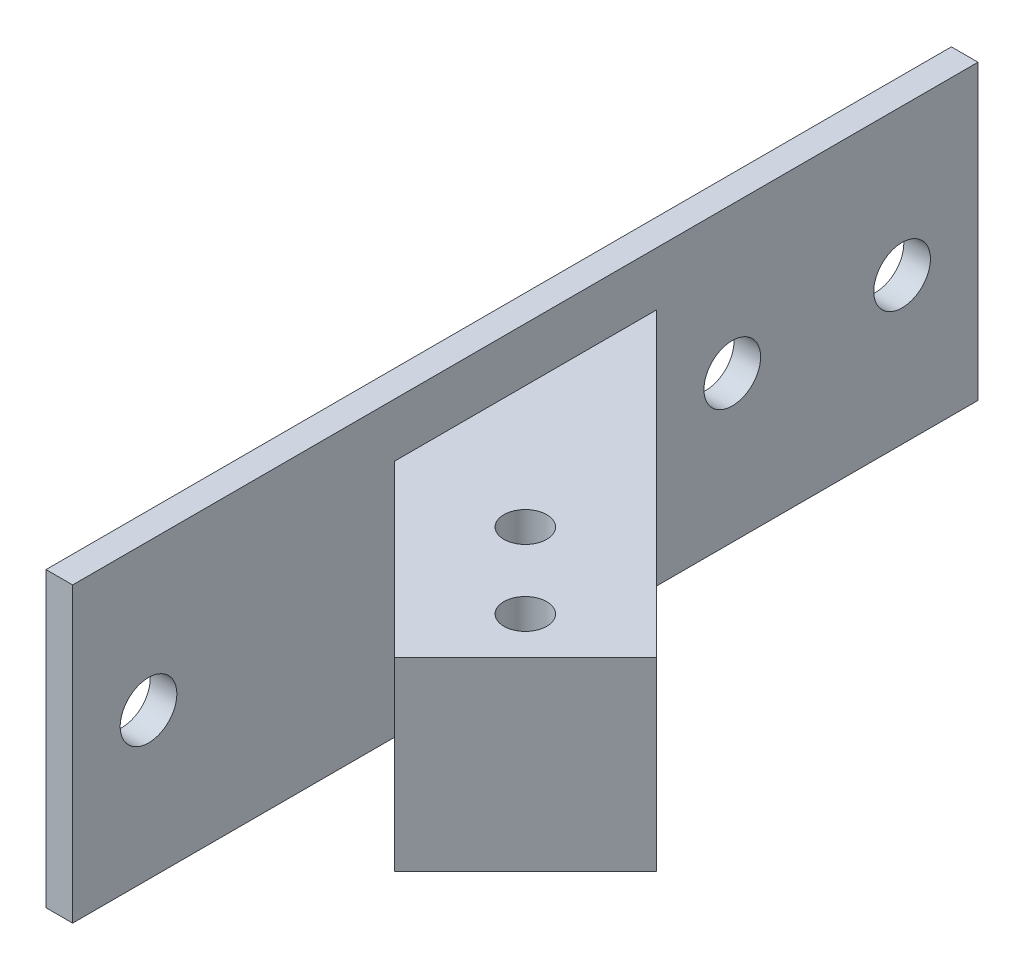
SolidWorks part; units mm, degrees
material "6061 Alloy"
ref_plane "Front" through (0, 0, 0) normal (0, 0, 1) x (1, 0, 0)
ref_plane "Top" through (0, 0, 0) normal (0, 1, 0) x (1, 0, 0)
ref_plane "Right" through (0, 0, 0) normal (1, 0, 0) x (0, 0, -1)
sketch "Sketch1" plane through (0, 0, 0) normal (1, 0, 0) x (0, 0, -1)
  line L1 (-53.975, 17.4625) -> (53.975, 17.4625)
  line L2 (-53.975, 17.4625) -> (-53.975, -17.4625)
  line L3 (-53.975, -17.4625) -> (53.975, -17.4625)
  line L4 (53.975, 17.4625) -> (53.975, -17.4625)
  line L5 (-53.975, 17.4625) -> (53.975, -17.4625) construction
  line L6 (-53.975, -17.4625) -> (53.975, 17.4625) construction
  point P0 (0, 0)
  dimension "D1" = 34.925
  dimension "D2" = 107.95
extrude "Boss-Extrude1" add sketch "Sketch1" along normal blind 3.175
sketch "Sketch3" plane through (0, 17.4625, 0) normal (0, 1, 0) x (1, 0, 0)
  line L0 (3.175, 0) -> (31.2383, -28.0633)
  line L1 (3.175, 53.975) -> (3.175, -53.975) construction
  line L2 (3.175, -20.2056) -> (21.1355, -38.1661)
  line L3 (3.175, 20.2056) -> (41.3411, -17.9605)
  line L4 (-3.9803, -13.0503) -> (21.1355, -38.1661) construction
  line L5 (16.2253, 7.1553) -> (41.3411, -17.9605) construction
  line L6 (6.1225, -2.9475) -> (31.2383, -28.0633) construction
  line L7 (21.1355, -38.1661) -> (31.2383, -28.0633)
  dimension "D1" = 14.2875
  dimension "D3" = 45
  dimension "D4" = 25.4
  dimension "D2" = 14.2875
sketch3d "3DSketch1"
  line L0 (3.175, 17.4625, 0) -> (31.2383, 17.4625, 28.0633) construction
sketch "Sketch4" plane through (29.6508, 0, 29.6508) normal (0.7071, 0, 0.7071) x (0.7071, 0, -0.7071)
  line L0 (2.2451, 17.4625) -> (2.2451, -17.4625) construction
  line L1 (-8.8039, -11.049) -> (13.2941, -11.049)
  line L2 (-8.8039, -11.049) -> (-8.8039, 11.049)
  line L3 (-8.8039, 11.049) -> (13.2941, 11.049)
  line L4 (13.2941, -11.049) -> (13.2941, 11.049)
  line L5 (-8.8039, -11.049) -> (13.2941, 11.049) construction
  line L6 (-8.8039, 11.049) -> (13.2941, -11.049) construction
  line L7 (40.4112, 17.4625) -> (-35.921, 17.4625) construction
  line L8 (-35.921, -17.4625) -> (40.4112, -17.4625) construction
  line L14 (-7.2164, 9.4615) -> (18.1836, -15.9385) construction
  line L15 (-10.4549, -12.7) -> (14.9451, 12.7) construction
  point P0 (2.2451, 0)
  point P12 (2.2451, 0)
  point P13 (2.2451, 0)
  dimension "D1" = 22.098
extrude "Boss-Extrude2" add sketch "Sketch4" against normal up to surface (28.6385 mm away) up to face at (3.175, 0, 0)
sketch "Sketch5" plane through (3.175, 0, 0) normal (1, 0, 0) x (0, 0, -1)
  line L0 (15.6256, 0) -> (24.6751, 0) construction
  line L1 (-53.975, 17.4625) -> (-53.975, -17.4625) construction
  line L2 (-44.9256, 0) -> (-53.975, 0) construction
  line L3 (-53.975, 0) -> (-35.8761, 0) construction
  line L4 (-35.8761, 11.049) -> (-35.8761, -11.049) construction
  line L5 (15.6256, 11.049) -> (15.6256, -11.049) construction
  line L6 (24.6751, 0) -> (44.9256, 0) construction
  line L7 (44.9256, 0) -> (53.975, 0) construction
  line L8 (53.975, -17.4625) -> (53.975, 17.4625) construction
  circle A0 centre (-44.9256, 0) radius 3.3782
  circle A1 centre (24.6751, 0) radius 3.3782
  circle A2 centre (44.9256, 0) radius 3.3782
  point P17 (-44.9256, 0)
  dimension "D2" = 6.7564
extrude "Cut-Extrude1" cut sketch "Sketch5" against normal up to next
sketch "Sketch6" plane through (0, 11.049, 0) normal (0, 1, 0) x (1, 0, 0)
  line L0 (31.2383, -28.0633) -> (26.7482, -23.5732) construction
  line L1 (39.0511, -20.2505) -> (23.4255, -35.8761) construction
  line L2 (31.2383, -28.0633) -> (17.7679, -14.5929) construction
  line L3 (23.4255, -35.8761) -> (5.465, -17.9156) construction
  line L4 (3.175, -15.6256) -> (23.4255, -35.8761) construction
  circle A0 centre (26.7482, -23.5732) radius 3.3782
  circle A1 centre (17.7679, -14.5929) radius 3.3782
  dimension "D1" = 6.35
  dimension "D2" = 6.7564
  dimension "D3" = 25.4
  dimension "D4" = 19.05
hole_wizard "1/4-20 Tapped Hole1" positions "Sketch7" profile "Sketch8" tap size "1/4-20" standard "ANSI Inch" end condition through all
sketch "Sketch7" plane through (0, 11.049, 0) normal (0, 1, 0) x (1, 0, 0)
  point P0 (17.7679, -14.5929)
  point P3 (26.7482, -23.5732)
sketch "Sketch8" plane through (17.7679, 11.049, 14.5929) normal (1, 0, 0) x (0, 0, 1)
  line L0 (0, 0) -> (0, 28.5115)
  line L1 (0, 28.5115) -> (2.5527, 28.5115)
  line L2 (2.5527, 28.5115) -> (2.5527, 0)
  line L5 (2.5527, 0) -> (0, 0)
  line L11 (0, -6.35) -> (0, 107.95) construction
  dimension "Thru Tap Drill Dia." = 5.1054
  dimension "Thru Tap Drill Depth" = 28.5115
